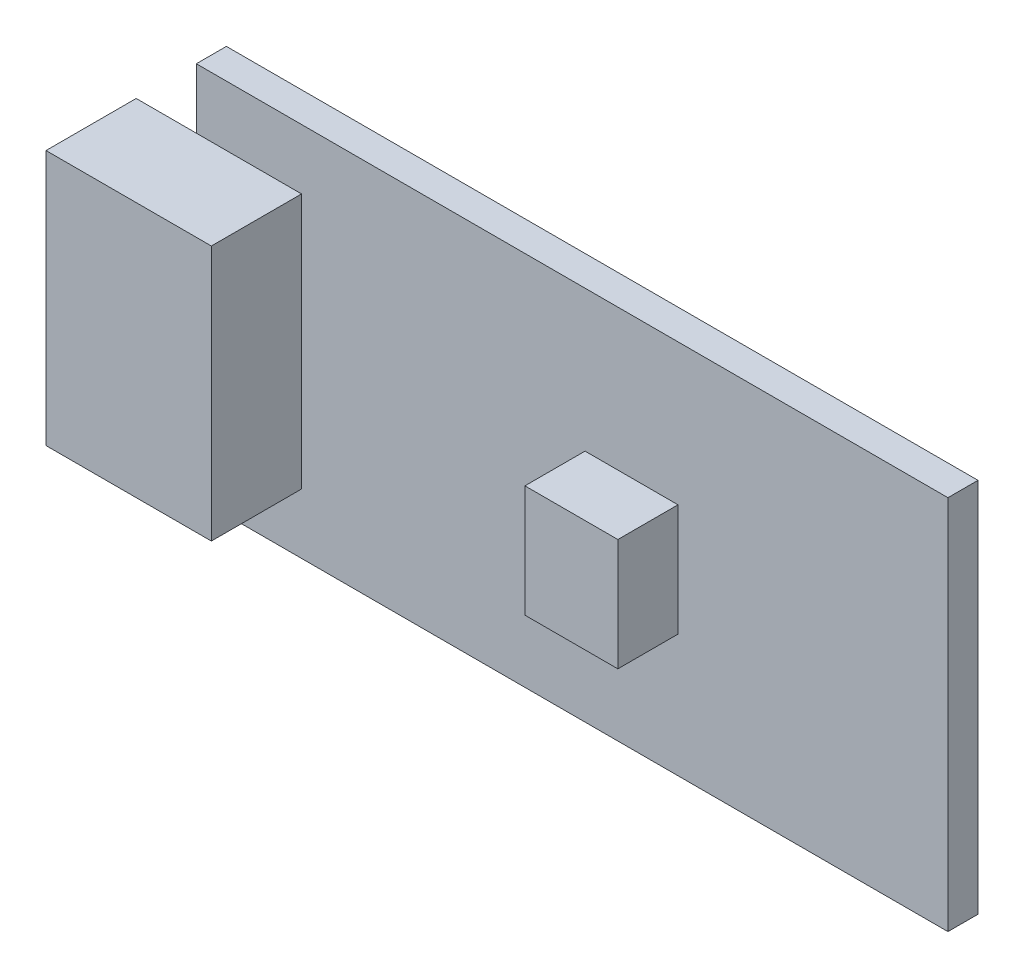
SolidWorks part; units mm, degrees
ref_plane "Ebene vorne" through (0, 0, 0) normal (0, 0, 1) x (1, 0, 0)
ref_plane "Ebene oben" through (0, 0, 0) normal (0, 1, 0) x (1, 0, 0)
ref_plane "Ebene rechts" through (0, 0, 0) normal (1, 0, 0) x (0, 0, -1)
sketch "Skizze1" plane through (0, 0, 0) normal (0, 0, 1) x (1, 0, 0)
  line L0 (19, 12.5) -> (19, 0) construction
  line L1 (0, 0) -> (25, 0)
  line L2 (0, 0) -> (0, 12.5)
  line L3 (0, 12.5) -> (25, 12.5)
  line L4 (25, 0) -> (25, 12.5)
  line L5 (9, 12.5) -> (9, 0) construction
  line L7 (12.9295, 7.8058) -> (16.0211, 7.8058)
  line L8 (12.9295, 7.8058) -> (12.9295, 4.0801)
  line L9 (12.9295, 4.0801) -> (16.0211, 4.0801)
  line L10 (16.0211, 7.8058) -> (16.0211, 4.0801)
  dimension "D1" = 12.5
  dimension "D2" = 25
  dimension "D3" = 6
  dimension "D4" = 10
extrude "Aufsatz-Linear austragen1" add sketch "Skizze1" along normal blind 1
extrude "Aufsatz-Linear austragen2" add sketch "Skizze1<2>" along normal blind 3 contours L10 L7 L8 L9 region at (14.4753, 5.9429, 0)
sketch "Skizze1<2>" plane through (0, 0, 0) normal (0, 0, 1) x (1, 0, 0) same geometry as "Skizze1"
sketch "Skizze2" plane through (0, 0, 1) normal (0, 0, 1) x (1, 0, 0)
  line L0 (-2, 6.25) -> (3.5, 6.25) construction
  line L1 (-2, 10.5) -> (3.5, 10.5)
  line L2 (-2, 10.5) -> (-2, 2)
  line L3 (-2, 2) -> (3.5, 2)
  line L4 (3.5, 10.5) -> (3.5, 2)
  line L5 (0, 12.5) -> (0, 0) construction
  point P6 (0, 6.25)
  dimension "D1" = 8.5
  dimension "D2" = 5.5
  dimension "D3" = 2
extrude "Aufsatz-Linear austragen3" add sketch "Skizze2" along normal blind 3 contours L4 L3 L2 L1
